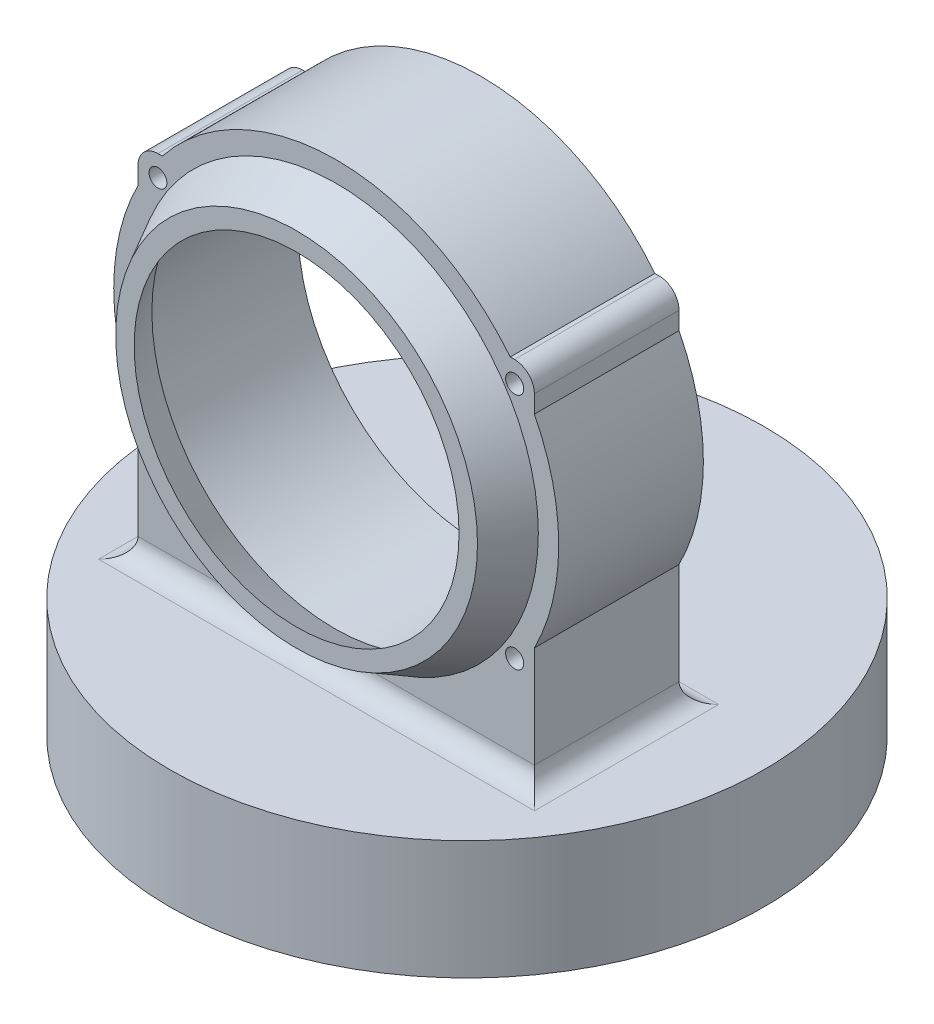
SolidWorks part; units mm, degrees
ref_plane "Alzado" through (0, 0, 0) normal (0, 0, 1) x (1, 0, 0)
ref_plane "Planta" through (0, 0, 0) normal (0, 1, 0) x (1, 0, 0)
ref_plane "Vista lateral" through (0, 0, 0) normal (1, 0, 0) x (0, 0, -1)
sketch "Croquis1" plane through (0, 0, 0) normal (0, 1, 0) x (1, 0, 0)
  circle A0 centre (0, 0) radius 75
  dimension "D1" = 150
extrude "Saliente-Extruir1" add sketch "Croquis1" along normal blind 30
sketch "Croquis3" plane through (0, 0, 0) normal (0, 0, 1) x (1, 0, 0)
  line L0 (43.907, 121.15) -> (45, 121.15)
  line L1 (50, 60.5996) -> (50, 30)
  line L2 (0, 0) -> (0, 85.4991) construction
  line L10 (-45, 121.15) -> (-43.907, 121.15)
  line L11 (-50, 116.15) -> (-50, 111.7004)
  line L12 (-50, 30) -> (50, 30)
  line L13 (50, 116.15) -> (50, 111.7004)
  line L14 (75, 30) -> (-75, 30) construction
  line L15 (-50, 60.5996) -> (-50, 30)
  circle A0 centre (0, 86.15) radius 46.15
  circle A1 centre (0, 86.15) radius 56.15
  arc A2 (45, 121.15) -> (50, 116.15) centre (45, 116.15) cw
  arc A3 (-45, 121.15) -> (-50, 116.15) centre (-45, 116.15) ccw
  point P5 (-0.8152, 30)
  point P17 (50, 121.15)
  point P20 (-50, 121.15)
  dimension "D4" = 92.3
  dimension "D6" = 5
  dimension "D1" = 100
  dimension "D2" = 10
  dimension "D3" = 35
  dimension "D5" = 50
extrude "Saliente-Extruir2" add sketch "Croquis3" against normal blind 36.5 from offset 33 contours A1 L15 L12 | A1 L12 L1 | L10 A3 L11 A1 | A2 L0 A1 L13 | A1 | A0 region at (47.8302, 117.6386, 0) region at (-47.8302, 117.6386, 0) region at (38.2791, 38.5026, 0) region at (-38.2791, 38.5026, 0)
sketch "Croquis5" plane through (0, 0, 33) normal (0, 0, 1) x (1, 0, 0)
  circle A0 centre (0, 86.15) radius 41
  circle A1 centre (0, 86.15) radius 51
  circle A2 centre (0, 86.15) radius 46.15 construction
  circle A3 centre (0, 86.15) radius 46.15 construction
  dimension "D1" = 82
  dimension "D2" = 10
extrude "Saliente-Extruir3" add sketch "Croquis5" along normal blind 10
chamfer "Chaflán1" distance 10 angle 28.15 1 edges at (41, 86.15, 33) first distance on face at (41, 86.15, 43)
chamfer "Chaflán2" distance 10 angle 28.15 1 edges at (51, 86.15, 43) first distance on face at (51, 86.15, 43)
fillet "Redondeo1" radius 5 4 edges at (0, 30, -3.5) (-50, 30, 14.75) (0, 30, 33) (50, 30, 14.75)
sketch "Croquis7" plane through (0, 0, -3.5) normal (0, 0, -1) x (-1, 0, 0)
  line L0 (0, 85.85) -> (71.2114, 85.85) construction
  circle A0 centre (44.9882, 115.8636) radius 2.2483
  circle A1 centre (-45.0262, 115.8636) radius 2.2831
  circle A2 centre (-45.0262, 55.8364) radius 2.2831
  circle A3 centre (44.9882, 55.8364) radius 2.2483
  dimension "D3" = 4.4965
  dimension "D1" = 30.0136
  dimension "D2" = 44.9882
extrude "Cortar-Extruir2" cut sketch "Croquis7" against normal through all
sketch "Croquis8" plane through (0, 0, 0) normal (0, -1, 0) x (1, 0, 0)
  circle A0 centre (0, 0) radius 61.2271
  circle A1 centre (26.0438, -11.3212) radius 2.5
  circle A2 centre (-24.6833, -14.0423) radius 2.5
  circle A3 centre (-26.0438, 11.3212) radius 2.5
  circle A4 centre (24.6833, 14.0423) radius 2.5
  dimension "D1" = 122.4541
  dimension "D2" = 5
extrude "Cortar-Extruir3" cut sketch "Croquis8" against normal blind 1.5 contours A0
extrude "Cortar-Extruir4" cut sketch "Croquis8<3>" against normal blind 10 contours A1 | A2 | A3 | A4
sketch "Croquis8<3>" plane through (0, 0, 0) normal (0, -1, 0) x (1, 0, 0) same geometry as "Croquis8"
